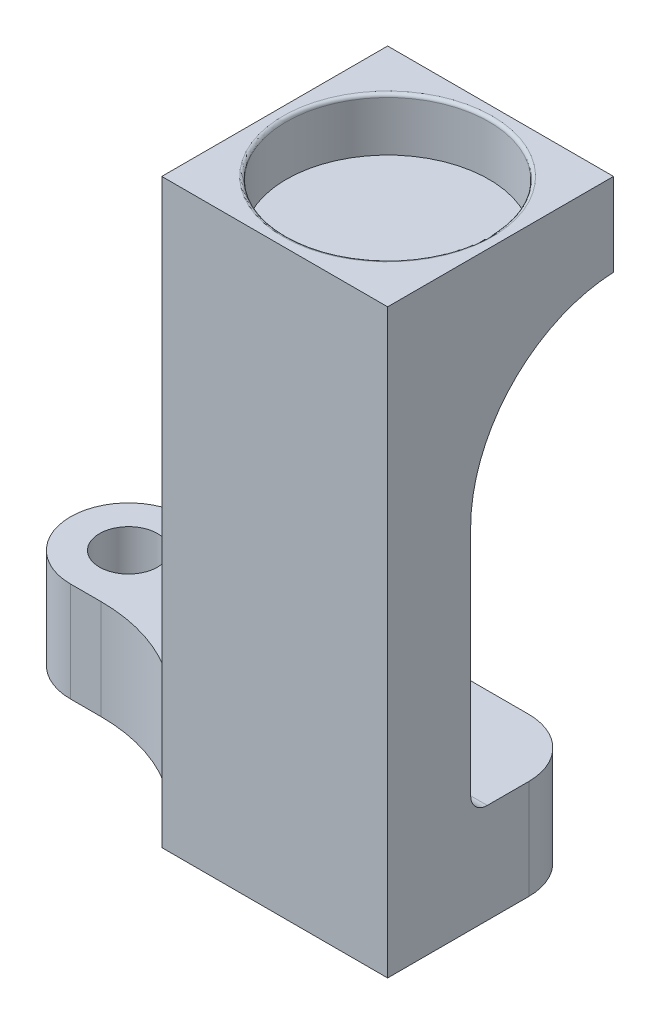
SolidWorks part; units mm, degrees
ref_plane "Front Plane" through (0, 0, 0) normal (0, 0, 1) x (1, 0, 0)
ref_plane "Top Plane" through (0, 0, 0) normal (0, 1, 0) x (1, 0, 0)
ref_plane "Right Plane" through (0, 0, 0) normal (1, 0, 0) x (0, 0, -1)
sketch "Sketch1" plane through (0, 0, 0) normal (0, 1, 0) x (1, 0, 0)
  line L1 (-6.8, 6.8) -> (6.8, 6.8)
  line L2 (-6.8, 6.8) -> (-6.8, -6.8)
  line L3 (-6.8, -6.8) -> (6.8, -6.8)
  line L4 (6.8, 6.8) -> (6.8, -6.8)
  line L5 (-6.8, 6.8) -> (6.8, -6.8) construction
  line L6 (-6.8, -6.8) -> (6.8, 6.8) construction
  point P0 (0, 0)
  dimension "D1" = 13.6
  dimension "D2" = 13.6
extrude "Boss-Extrude1" add sketch "Sketch1" along normal blind 5
sketch "Sketch2" plane through (0, 5, 0) normal (0, 1, 0) x (1, 0, 0)
  circle A0 centre (0, 0) radius 6.1
  dimension "D1" = 12.2
extrude "Cut-Extrude1" cut sketch "Sketch2" against normal blind 3.2
sketch "Sketch3" plane through (0, 0, 0) normal (0, -1, 0) x (1, 0, 0)
  line L0 (6.8, 6.8) -> (6.8, -6.8) construction
  line L1 (-6.8, 6.8) -> (6.8, 6.8)
  line L2 (-6.8, 6.8) -> (-6.8, 1.8)
  line L3 (-6.8, 1.8) -> (6.8, 1.8)
  line L4 (6.8, 6.8) -> (6.8, 1.8)
  dimension "D1" = 5
extrude "Boss-Extrude2" add sketch "Sketch3" along normal blind 30
sketch "Sketch4" plane through (0, 1.8, 0) normal (0, 1, 0) x (1, 0, 0)
  point P0 (0, 0)
fillet "Fillet1" radius 0.2 1 edges at (0, 5, 6.1)
fillet "Fillet2" radius 9 1 edges at (0, 0, 1.8)
sketch "Sketch10" plane through (0, 0, 1.8) normal (0, 0, -1) x (-1, 0, 0)
  line L1 (-6.8, -30) -> (20.8, -30)
  line L2 (-6.8, -30) -> (-6.8, -24)
  line L3 (-6.8, -24) -> (20.8, -24)
  line L4 (20.8, -30) -> (20.8, -24)
  dimension "D1" = 6
  dimension "D2" = 27.6
extrude "Boss-Extrude5" add sketch "Sketch10" along normal blind 7
sketch "Sketch11" plane through (0, -24, 0) normal (0, 1, 0) x (1, 0, 0)
  line L0 (-6.8, -1.8) -> (-6.8, 5.2) construction
  line L1 (-20.8, 5.2) -> (6.8, 5.2) construction
  line L2 (-6.8, 1.7) -> (-10.3, 1.7) construction
  line L3 (-10.3, 1.7) -> (-13.8, 1.7) construction
  line L4 (-17.3, 1.7) -> (-20.8, 1.7) construction
  line L5 (-20.8, 5.2) -> (-20.8, -1.8) construction
  line L6 (-13.8, 1.7) -> (-17.3, 1.7) construction
  circle A0 centre (-10.3, 1.7) radius 1.75
  circle A1 centre (-17.3, 1.7) radius 1.75
  dimension "D1" = 3.5
  dimension "D2" = 3.5
extrude "Cut-Extrude4" cut sketch "Sketch11" against normal through all
sketch "Sketch12" plane through (0, -24, 0) normal (0, 1, 0) x (1, 0, 0)
  line L0 (-10.3, 3.45) -> (-10.3, -0.05)
  circle A0 centre (-10.3, 1.7) radius 1.75
  point P4 (-10.3, 1.7)
fillet "Fillet3" radius 10 1 edges at (-6.8, -27, 1.8)
fillet "Fillet4" radius 3.5 3 edges at (-20.8, -27, 1.8) (-20.8, -27, -5.2) (6.8, -27, -5.2)
fillet "Fillet5" radius 1 2 edges at (-6.8, -24, 4.3) (0, -24, 1.8)
mirror "Mirror1" [suppressed] of bodies 109
delete or keep bodies "Body-Delete/Keep 1" [suppressed] type delete bodies bodies 109
